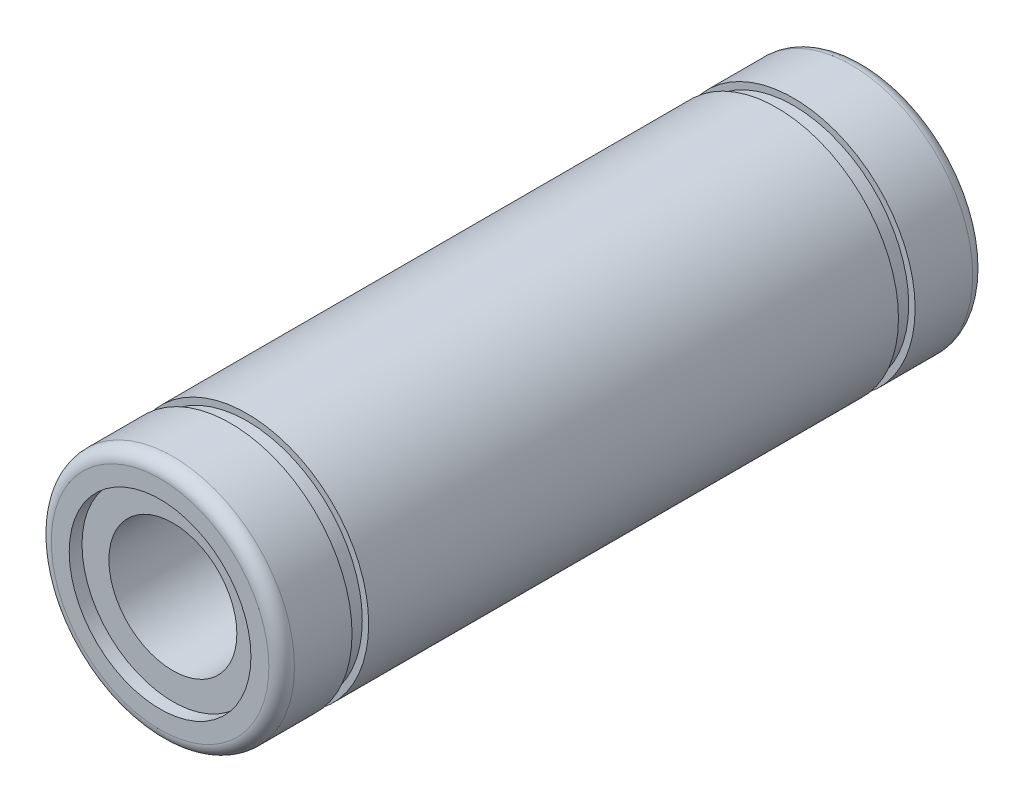
SolidWorks part; units mm, degrees
ref_plane "Front Plane" through (0, 0, 0) normal (0, 0, 1) x (1, 0, 0)
ref_plane "Top Plane" through (0, 0, 0) normal (0, 1, 0) x (1, 0, 0)
ref_plane "Right Plane" through (0, 0, 0) normal (1, 0, 0) x (0, 0, -1)
sketch "Sketch1" plane through (0, 0, 0) normal (0, 0, 1) x (1, 0, 0)
  circle A0 centre (0, 0) radius 5
  circle A1 centre (0, 0) radius 9.5
  dimension "D1" = 19
  dimension "D2" = 10
extrude "Boss-Extrude1" add sketch "Sketch1" along normal blind 55
sketch "Sketch2" plane through (0, 0, 55) normal (0, 0, 1) x (1, 0, 0)
  circle A0 centre (0, 0) radius 7.1
  dimension "D1" = 14.2
extrude "Cut-Extrude1" cut sketch "Sketch2" against normal blind 1
sketch "Sketch3" plane through (0, 0, 0) normal (0, 0, -1) x (-1, 0, 0)
  circle A0 centre (0, 0) radius 7.1
  dimension "D1" = 14.2
extrude "Cut-Extrude2" cut sketch "Sketch3" against normal blind 1
sketch "Sketch4" plane through (0, 0, 0) normal (0, 1, 0) x (1, 0, 0)
  line L0 (-9.5, 0) -> (-9.5, -55) construction
  line L1 (0, 0) -> (0, -55) construction
  line L2 (-9.5, -55) -> (9.5, -55) construction
  line L3 (-9.5, -49.5) -> (-9, -49.5)
  line L4 (-9.5, -49.5) -> (-9.5, -48.2)
  line L5 (-9.5, -48.2) -> (-9, -48.2)
  line L6 (-9, -49.5) -> (-9, -48.2)
  line L7 (9.5, -27.5) -> (-9.5, -27.5) construction
  line L8 (-9.5, -5.5) -> (-9, -5.5)
  line L9 (-9.5, -5.5) -> (-9.5, -6.8)
  line L10 (-9.5, -6.8) -> (-9, -6.8)
  line L11 (-9, -5.5) -> (-9, -6.8)
  line L12 (9.5, -55) -> (9.5, 0) construction
  line L13 (-9, -6.8) -> (-9, -48.2) construction
  point P19 (-9, -27.5)
  dimension "D1" = 1.3
  dimension "D2" = 1.3
  dimension "D3" = 44
  dimension "D4" = 9
ref_axis "Axis1" through (0, 0, 54) along (0, 0, -1)
revolve "Cut-Revolve1" cut sketch "Sketch4" angle 360 about L1
fillet "Fillet1" radius 1 2 edges at (9.5, 0, 55) (9.5, 0, 0)
